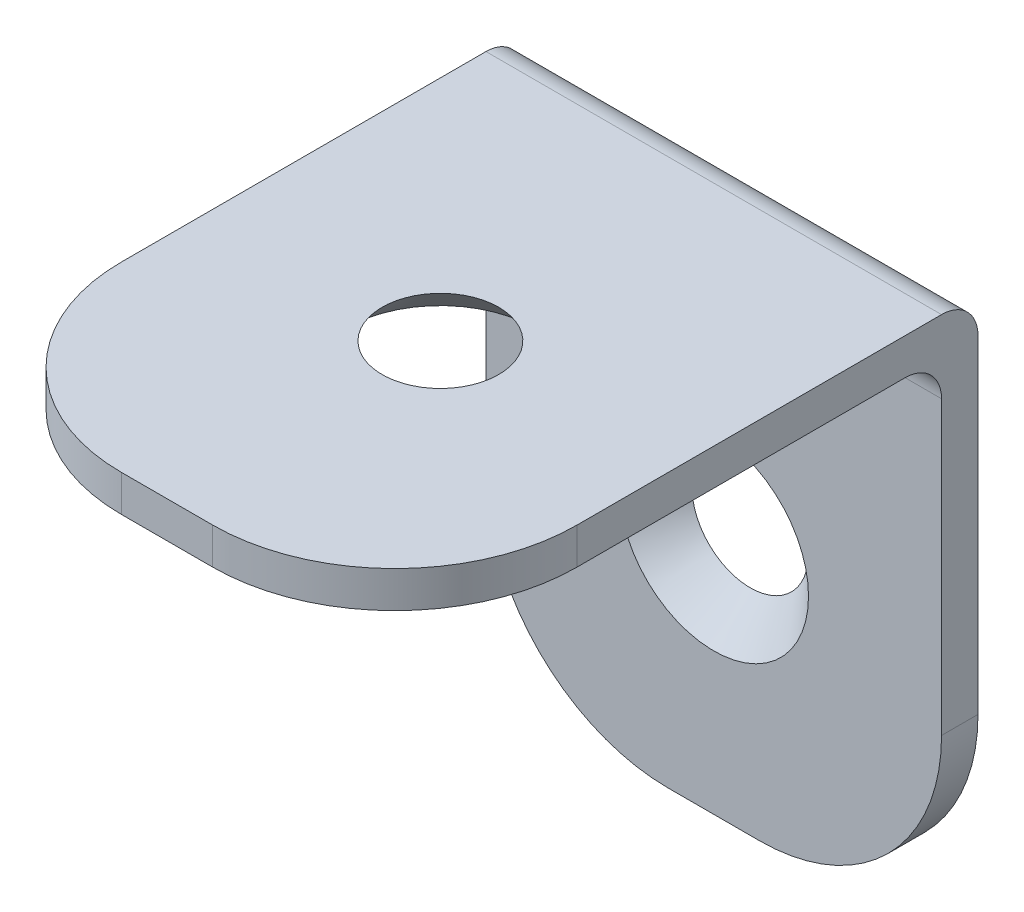
SolidWorks part; units mm, degrees
ref_plane "Спереди" through (0, 0, 0) normal (0, 0, 1) x (1, 0, 0)
ref_plane "Сверху" through (0, 0, 0) normal (0, 1, 0) x (1, 0, 0)
ref_plane "Справа" through (0, 0, 0) normal (1, 0, 0) x (0, 0, -1)
sketch "Эскиз1" plane through (0, 0, 0) normal (0, 1, 0) x (1, 0, 0)
  line L1 (-2.5, -15) -> (2.5, -15)
  line L2 (-12.5, -5) -> (-12.5, 15)
  line L3 (-12.5, 15) -> (12.5, 15)
  line L4 (12.5, -5) -> (12.5, 15)
  line L5 (-12.5, -15) -> (12.5, 15) construction
  line L6 (-12.5, 15) -> (12.5, -15) construction
  arc A0 (2.5, -15) -> (12.5, -5) centre (2.5, -5) ccw
  arc A1 (-2.5, -15) -> (-12.5, -5) centre (-2.5, -5) cw
  point P0 (0, 0)
  dimension "D3" = 10
  dimension "D1" = 25
  dimension "D2" = 30
extrude "Бобышка-Вытянуть1" add sketch "Эскиз1" along normal blind 2
sketch "Эскиз3" plane through (0, 0, -15) normal (0, 0, -1) x (-1, 0, 0)
  line L0 (-2.5, -28) -> (2.5, -28)
  line L1 (-12.5, -18) -> (-12.5, 2)
  line L2 (-12.5, 2) -> (12.5, 2)
  line L3 (12.5, -18) -> (12.5, 2)
  line L4 (-12.5, 0) -> (12.5, 0) construction
  arc A0 (2.5, -28) -> (12.5, -18) centre (2.5, -18) ccw
  arc A1 (-2.5, -28) -> (-12.5, -18) centre (-2.5, -18) cw
  dimension "D1" = 28
  dimension "D2" = 25
extrude "Бобышка-Вытянуть2" add sketch "Эскиз3" along normal blind 2
fillet "Скругление1" radius 2 1 edges at (0, 0, -15)
fillet "Скругление2" radius 2 1 edges at (0, 2, -17)
hole_wizard "Зенковка для винта с полупотайной головкой M52" positions "Эскиз6" profile "Эскиз7" countersink size "M5" standard "ISO" end condition through all
sketch "Эскиз6" plane through (0, 0, -15) normal (0, 0, 1) x (1, 0, 0)
  point P0 (0, -15.0342)
sketch "Эскиз7" plane through (0, -15.0342, -15) normal (1, 0, 0) x (0, -1, 0)
  line L0 (0, 0) -> (0, 2)
  line L1 (0, 2) -> (2.75, 2)
  line L2 (2.75, 2) -> (2.75, 2.45)
  line L3 (2.75, 2.45) -> (5.2, 0)
  line L5 (5.2, 0) -> (0, 0)
  line L6 (-2.75, 2.45) -> (-5.2, 0) construction
  line L11 (0, -6.35) -> (0, 107.95) construction
  dimension "Диаметр сквозного отверстия" = 5.5
  dimension "Глубина сквозного отверстия" = 2
  dimension "Диаметр передней зенковки" = 10.4
  dimension "Угол передней зенковки" = 90
hole_wizard "Зенковка для винта с полупотайной головкой M53" positions "Эскиз8" profile "Эскиз9" countersink size "M5" standard "ISO" end condition through all
sketch "Эскиз8" plane through (0, 0, 0) normal (0, -1, 0) x (-1, 0, 0)
  point P0 (0, 0)
sketch "Эскиз9" plane through (0, 0, 0) normal (1, 0, 0) x (0, 0, -1)
  line L0 (0, 0) -> (0, 2)
  line L1 (0, 2) -> (2.75, 2)
  line L2 (2.75, 2) -> (2.75, 2.45)
  line L3 (2.75, 2.45) -> (5.2, 0)
  line L5 (5.2, 0) -> (0, 0)
  line L6 (-2.75, 2.45) -> (-5.2, 0) construction
  line L11 (0, -6.35) -> (0, 107.95) construction
  dimension "Диаметр сквозного отверстия" = 5.5
  dimension "Глубина сквозного отверстия" = 2
  dimension "Диаметр передней зенковки" = 10.4
  dimension "Угол передней зенковки" = 90
